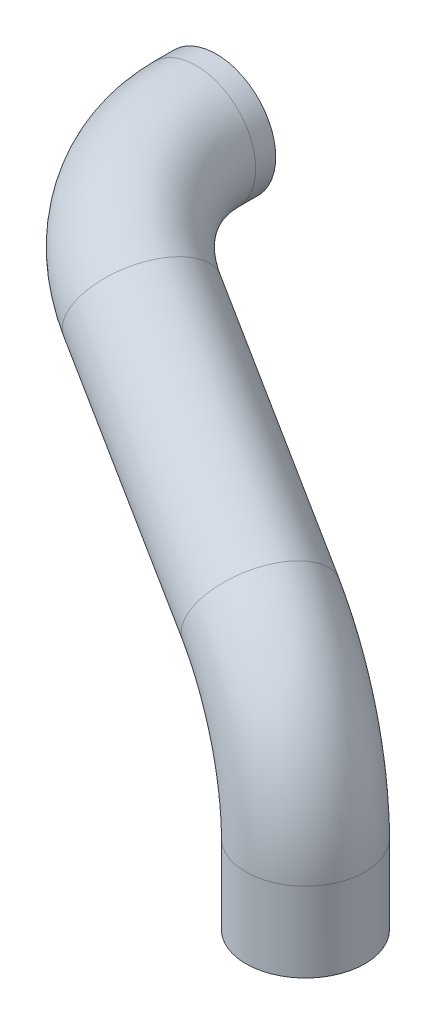
SolidWorks part; units mm, degrees
ref_plane "前视基准面" through (0, 0, 0) normal (0, 0, 1) x (1, 0, 0)
ref_plane "上视基准面" through (0, 0, 0) normal (0, 1, 0) x (1, 0, 0)
ref_plane "右视基准面" through (0, 0, 0) normal (1, 0, 0) x (0, 0, -1)
other "Configuration Table"
sketch3d "3D草图2"
  line L0 (0, 0, 0) -> (0, 13.3701, 0)
  line L1 (-65, 60, -50) -> (-65, 60, -46.6299)
  line L2 (-51.074, 53.5726, -23.5726) -> (-13.926, 36.4274, -6.4274)
  arc A0 (-65, 60, -46.6299) -> (-51.074, 53.5726, -23.5726) centre (-42.301, 49.5235, -46.6299) ccw
  arc A1 (0, 13.3701, 0) -> (-13.926, 36.4274, -6.4274) centre (-22.699, 13.3701, -10.4765) ccw
  point P5 (-33.0264, 66.9023, -89.8663)
  point P6 (-65, 60, -33.7652)
  point P9 (-65, 60, -30)
  point P10 (-31.8246, 72.2225, -46.6299)
  point P13 (0, 30, 0)
  point P14 (-33.1754, 13.3701, 12.2225)
  dimension "D3" = 65
  dimension "D5" = 50
  dimension "D6" = 25
  dimension "D1" = 30
  dimension "D2" = 60
  dimension "D4" = 20
sweep "扫描-薄件1" add path "3D草图2" circular profile diameter 20 parameters "D1"=2.5, "D3"=20
